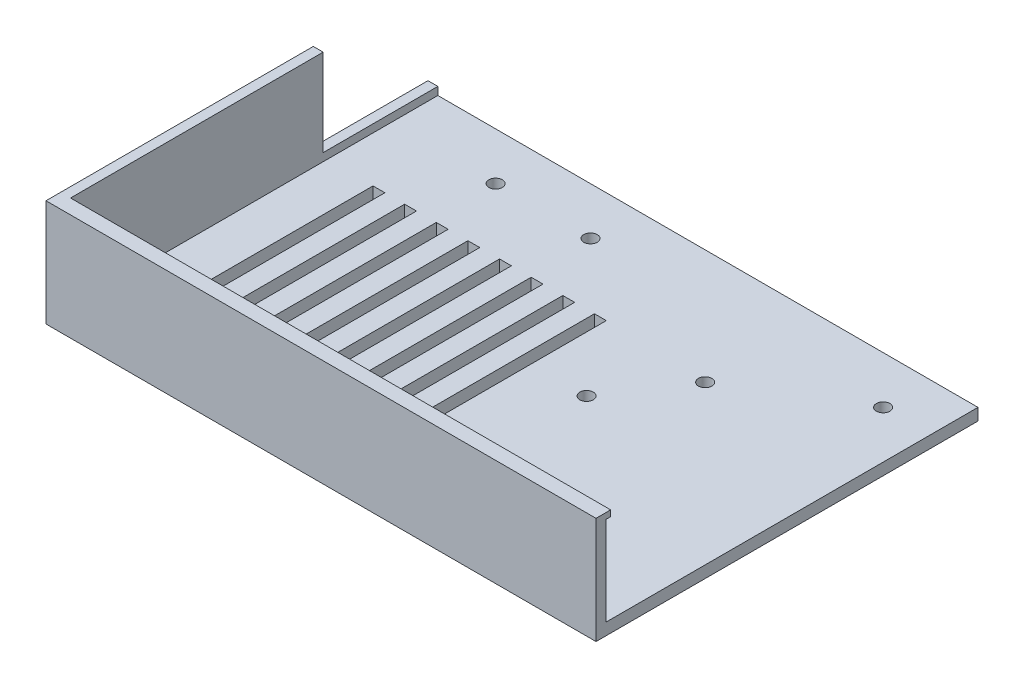
SolidWorks part; units mm, degrees
ref_plane "Front Plane" through (0, 0, 0) normal (0, 0, 1) x (1, 0, 0)
ref_plane "Top Plane" through (0, 0, 0) normal (0, 1, 0) x (1, 0, 0)
ref_plane "Right Plane" through (0, 0, 0) normal (1, 0, 0) x (0, 0, -1)
sketch "Sketch1" plane through (0, 0, 0) normal (0, 1, 0) x (1, 0, 0)
  line L1 (-139.1, -96.6) -> (139.1, -96.6)
  line L2 (-139.1, -96.6) -> (-139.1, 96.6)
  line L3 (-139.1, 96.6) -> (139.1, 96.6)
  line L4 (139.1, -96.6) -> (139.1, 96.6)
  line L5 (-139.1, -96.6) -> (139.1, 96.6) construction
  line L6 (-139.1, 96.6) -> (139.1, -96.6) construction
  point P0 (0, 0)
  dimension "D1" = 278.2
  dimension "D2" = 193.2
extrude "Shell Block" add sketch "Sketch1" along normal blind 27
ref_plane "Shell Front" through (0, 27, 0) normal (0, 1, 0) x (1, 0, 0)
sketch "Sketch2" plane through (0, 27, 0) normal (0, 1, 0) x (1, 0, 0)
  line L1 (-136.6, -92.9) -> (136.6, -92.9)
  line L2 (-136.6, -92.9) -> (-136.6, 92.9)
  line L3 (-136.6, 92.9) -> (136.6, 92.9)
  line L4 (136.6, -92.9) -> (136.6, 92.9)
  line L5 (-136.6, -92.9) -> (136.6, 92.9) construction
  line L6 (-136.6, 92.9) -> (136.6, -92.9) construction
  point P0 (0, 0)
  dimension "D1" = 273.2
  dimension "D2" = 185.8
extrude "Front Opening" cut sketch "Sketch2" against normal blind 1.5
ref_plane "Under Lip" through (0, 25.5, 0) normal (0, 1, 0) x (1, 0, 0)
sketch "Sketch3" plane through (0, 25.5, 0) normal (0, 1, 0) x (1, 0, 0)
  line L1 (-136.6, -94.1) -> (136.6, -94.1)
  line L2 (-136.6, -94.1) -> (-136.6, 94.1)
  line L3 (-136.6, 94.1) -> (136.6, 94.1)
  line L4 (136.6, -94.1) -> (136.6, 94.1)
  line L5 (-136.6, -94.1) -> (136.6, 94.1) construction
  line L6 (-136.6, 94.1) -> (136.6, -94.1) construction
  point P0 (0, 0)
  dimension "D1" = 273.2
  dimension "D2" = 188.2
extrude "Display Pocket" cut sketch "Sketch3" against normal blind 22.5
ref_plane "Back Inner" through (0, 3, 0) normal (0, 1, 0) x (1, 0, 0)
sketch "Sketch4" plane through (0, 3, 0) normal (0, 1, 0) x (1, 0, 0)
  line L1 (-69, 28) -> (-66, 28)
  line L2 (-69, 28) -> (-69, 84)
  line L3 (-69, 84) -> (-66, 84)
  line L4 (-66, 28) -> (-66, 84)
  line L6 (-69, -84) -> (-66, -84)
  line L7 (-69, -84) -> (-69, -28)
  line L8 (-69, -28) -> (-66, -28)
  line L9 (-66, -84) -> (-66, -28)
  line L11 (-77, 28) -> (-74, 28)
  line L12 (-77, 28) -> (-77, 84)
  line L13 (-77, 84) -> (-74, 84)
  line L14 (-74, 28) -> (-74, 84)
  line L16 (-77, -84) -> (-74, -84)
  line L17 (-77, -84) -> (-77, -28)
  line L18 (-77, -28) -> (-74, -28)
  line L19 (-74, -84) -> (-74, -28)
  line L21 (-85, 28) -> (-82, 28)
  line L22 (-85, 28) -> (-85, 84)
  line L23 (-85, 84) -> (-82, 84)
  line L24 (-82, 28) -> (-82, 84)
  line L26 (-85, -84) -> (-82, -84)
  line L27 (-85, -84) -> (-85, -28)
  line L28 (-85, -28) -> (-82, -28)
  line L29 (-82, -84) -> (-82, -28)
  line L31 (-93, 28) -> (-90, 28)
  line L32 (-93, 28) -> (-93, 84)
  line L33 (-93, 84) -> (-90, 84)
  line L34 (-90, 28) -> (-90, 84)
  line L36 (-93, -84) -> (-90, -84)
  line L37 (-93, -84) -> (-93, -28)
  line L38 (-93, -28) -> (-90, -28)
  line L39 (-90, -84) -> (-90, -28)
  line L41 (-101, 28) -> (-98, 28)
  line L42 (-101, 28) -> (-101, 84)
  line L43 (-101, 84) -> (-98, 84)
  line L44 (-98, 28) -> (-98, 84)
  line L46 (-101, -84) -> (-98, -84)
  line L47 (-101, -84) -> (-101, -28)
  line L48 (-101, -28) -> (-98, -28)
  line L49 (-98, -84) -> (-98, -28)
  line L51 (-109, 28) -> (-106, 28)
  line L52 (-109, 28) -> (-109, 84)
  line L53 (-109, 84) -> (-106, 84)
  line L54 (-106, 28) -> (-106, 84)
  line L56 (-109, -84) -> (-106, -84)
  line L57 (-109, -84) -> (-109, -28)
  line L58 (-109, -28) -> (-106, -28)
  line L59 (-106, -84) -> (-106, -28)
  line L61 (-117, 28) -> (-114, 28)
  line L62 (-117, 28) -> (-117, 84)
  line L63 (-117, 84) -> (-114, 84)
  line L64 (-114, 28) -> (-114, 84)
  line L66 (-117, -84) -> (-114, -84)
  line L67 (-117, -84) -> (-117, -28)
  line L68 (-117, -28) -> (-114, -28)
  line L69 (-114, -84) -> (-114, -28)
  line L71 (-125, 28) -> (-122, 28)
  line L72 (-125, 28) -> (-125, 84)
  line L73 (-125, 84) -> (-122, 84)
  line L74 (-122, 28) -> (-122, 84)
  line L76 (-125, -84) -> (-122, -84)
  line L77 (-125, -84) -> (-125, -28)
  line L78 (-125, -28) -> (-122, -28)
  line L79 (-122, -84) -> (-122, -28)
extrude "Vent Slots" cut sketch "Sketch4" against normal blind 4
sketch "Sketch5" plane through (0, 0, 0) normal (1, 0, 0) x (0, 0, -1)
  line L1 (-29, 5) -> (29, 5)
  line L2 (-29, 5) -> (-29, 28)
  line L3 (-29, 28) -> (29, 28)
  line L4 (29, 5) -> (29, 28)
extrude "Cable Exit (-X short side)" cut sketch "Sketch5" against normal blind 140.1
sketch "Sketch6" plane through (0, 3, 0) normal (0, 1, 0) x (1, 0, 0)
  circle A0 centre (-40, -29) radius 1.7
  circle A1 centre (-40, -89) radius 1.7
  circle A2 centre (40, -29) radius 1.7
  circle A3 centre (40, -89) radius 1.7
  circle A4 centre (-52, -47) radius 1.7
  circle A5 centre (-52, -71) radius 1.7
  circle A6 centre (52, -47) radius 1.7
  circle A7 centre (52, -71) radius 1.7
  circle A8 centre (-12, 82) radius 1.7
  circle A9 centre (12, 82) radius 1.7
  circle A10 centre (124, 12) radius 1.7
  circle A11 centre (124, -12) radius 1.7
  circle A12 centre (-12, 12) radius 1.7
  circle A13 centre (-12, -12) radius 1.7
  circle A14 centre (12, 12) radius 1.7
  circle A15 centre (12, -12) radius 1.7
  circle A16 centre (-110, -12) radius 1.7
  circle A17 centre (-110, 12) radius 1.7
  circle A18 centre (-86, -12) radius 1.7
  circle A19 centre (-86, 12) radius 1.7
extrude "Bolt Holes" cut sketch "Sketch6" against normal blind 4
sketch "Sketch7" plane through (0, 0, 0) normal (0, 1, 0) x (1, 0, 0)
  line L1 (200, -200) -> (0, -200)
  line L2 (200, -200) -> (200, 200)
  line L3 (200, 200) -> (0, 200)
  line L4 (0, -200) -> (0, 200)
extrude "Keep one half (X)" cut sketch "Sketch7" against normal through all and the other way through all
sketch "Sketch8" plane through (0, 0, 0) normal (0, 1, 0) x (1, 0, 0)
  line L1 (-200, 0) -> (200, 0)
  line L2 (-200, 0) -> (-200, 200)
  line L3 (-200, 200) -> (200, 200)
  line L4 (200, 0) -> (200, 200)
extrude "Keep one quarter (Z)" cut sketch "Sketch8" against normal through all and the other way through all
equation "\"DispL\"= 272.0"
equation "\"DispW\"= 187.0"
equation "\"DispT\"= 20.0"
equation "\"Clr\"= 0.6"
equation "\"Wall\"= 2.5"
equation "\"BackT\"= 3.0"
equation "\"CableRoom\"= 4.0"
equation "\"LipW\"= 1.2"
equation "\"LipT\"= 1.5"
equation "\"CableW\"= 58.0"
equation "\"CableH\"= 16.0"
equation "\"BoltD\"= 3.4"
equation "\"ShellL\"= \"DispL\" + 2 * \"Clr\" + 2 * \"Wall\""
equation "\"ShellW\"= \"DispW\" + 2 * \"Clr\" + 2 * \"Wall\""
equation "\"ShellH\"= \"BackT\" + \"DispT\" + \"CableRoom\""
equation "\"D1@Sketch1\" = \"ShellL\""
equation "\"D2@Sketch1\" = \"ShellW\""
equation "\"D1@Shell Block\" = \"ShellH\""
equation "\"D1@Shell Front\" = \"ShellH\""
equation "\"D1@Sketch2\" = \"DispL\" + 2 * \"Clr\""
equation "\"D2@Sketch2\" = \"DispW\" + 2 * \"Clr\" - 2 * \"LipW\""
equation "\"D1@Front Opening\" = \"LipT\""
equation "\"D1@Under Lip\" = \"ShellH\" - \"LipT\""
equation "\"D1@Sketch3\" = \"DispL\" + 2 * \"Clr\""
equation "\"D2@Sketch3\" = \"DispW\" + 2 * \"Clr\""
equation "\"D1@Display Pocket\" = \"ShellH\" - \"LipT\" - \"BackT\""
equation "\"D1@Back Inner\" = \"BackT\""
